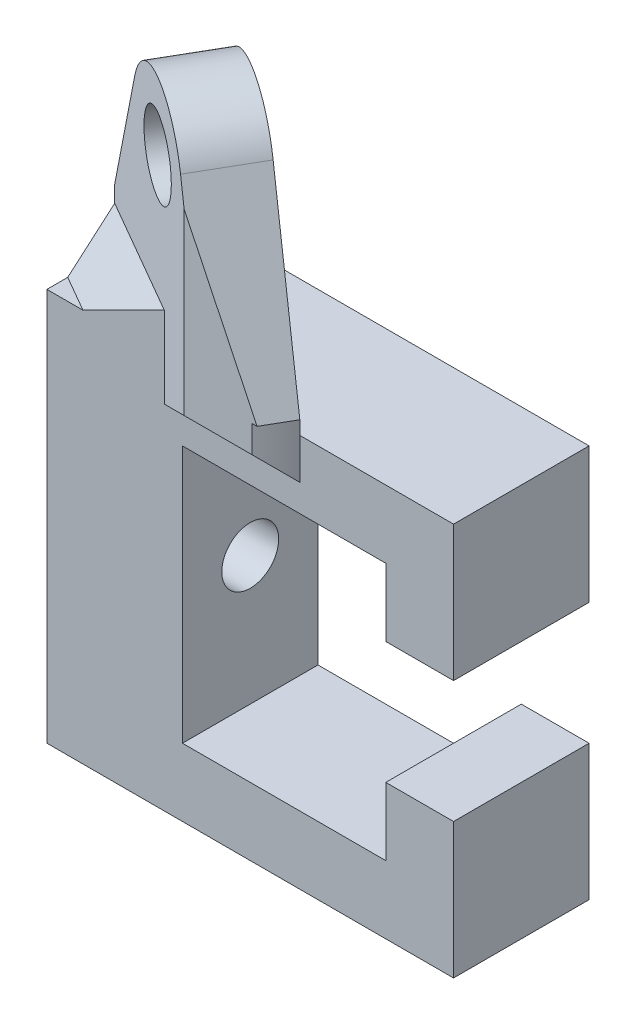
SolidWorks part; units mm, degrees
note: '?' marks a value the reader was unsure of.
ref_plane "Front Plane" through (0, 0, 0) normal (0, 0, 1) x (1, 0, 0)
ref_plane "Top Plane" through (0, 0, 0) normal (0, 1, 0) x (1, 0, 0)
ref_plane "Right Plane" through (0, 0, 0) normal (1, 0, 0) x (0, 0, -1)
sketch "Sketch1" plane through (0, 0, 0) normal (0, 0, 1) x (1, 0, 0)
  line L0 (0, 0) -> (0, -23031.2068) construction
  line L1 (0, 0) -> (23031.2068, 0) construction
  line L2 (15, 5) -> (15, 0)
  line L3 (15, 0) -> (0, 0)
  line L4 (0, 0) -> (0, 19)
  line L5 (0, 19) -> (15, 19)
  line L6 (15, 19) -> (15, 14)
  line L7 (15, 14) -> (20, 14)
  line L8 (20, 14) -> (20, 24)
  line L9 (20, 24) -> (-10, 24)
  line L10 (-10, 24) -> (-10, -5)
  line L11 (-10, -5) -> (20, -5)
  line L12 (20, -5) -> (20, 5)
  line L13 (20, 5) -> (15, 5)
  dimension "D1" = 19
  dimension "D2" = 15
  dimension "D3" = 15
  dimension "D4" = 5
  dimension "D5" = 5
  dimension "D6" = 5
  dimension "D7" = 5
  dimension "D8" = 5
  dimension "D9" = 10
extrude "Boss-Extrude1" add sketch "Sketch1" along normal mid plane 10
sketch "Sketch2" plane through (-10, 0, 0) normal (-1, 0, 0) x (0, 0, 1)
  line L0 (0, 24) -> (0, -49976) construction
  line L1 (5, 24) -> (-5, 24) construction
  line L2 (-5, 9.5) -> (49995, 9.5) construction
  line L3 (-5, 24) -> (-5, -5) construction
  circle A0 centre (0, 9.5) radius 2.1
  point P4 (0, 24)
  point P9 (-5, 9.5)
  dimension "D1" = 4.2
extrude "Cut-Extrude1" cut sketch "Sketch2" against normal blind 10
sketch "Sketch3" plane through (0, 24, 0) normal (0, 1, 0) x (1, 0, 0)
  line L0 (0, -5) -> (0, 5) construction
  line L1 (0, -5) -> (0, 5) construction
  circle A0 centre (0, 0) radius 10
  dimension "D1" = 20
extrude "Boss-Extrude2" add sketch "Sketch3" along normal blind 1
ref_axis "Axis1" through (0, 30.7, 0) along (0, -1, 0)?
ref_plane "Plane1" through (0, 0, 0) normal (-0.5, 0, 0.866) x (0, -1, 0)
sketch "Sketch4" plane through (0, 0, 0) normal (-0.5, 0, 0.866) x (0.866, 0, 0.5)
  line L0 (10, 25) -> (-10, 25) construction
  line L1 (10, 25) -> (-10, 25)
  line L2 (0, 29) -> (0, 50029) construction
  line L3 (-10, 25) -> (-4.6154, 37.9231)
  line L4 (10, 25) -> (4.6154, 37.9231)
  circle A0 centre (0, 36) radius 2.75
  circle A1 centre (0, 36) radius 10 construction
  arc A3 (4.6154, 37.9231) -> (-4.6154, 37.9231) centre (0, 36) ccw
  point P4 (0, 25)
  dimension "D1" = 5.5
  dimension "D2" = 20
  dimension "D3" = 11
  dimension "D4" = 10
extrude "Boss-Extrude3" add sketch "Sketch4" along normal blind 5
sketch "Sketch5" plane through (0, -5, 0) normal (0, -1, 0) x (1, 0, 0)
  line L0 (-20, -15) -> (30, -15)
  line L1 (30, -15) -> (30, 15)
  line L2 (30, 15) -> (-20, 15)
  line L3 (-20, 15) -> (-20, -15)
  line L4 (-10, -5) -> (20, -5)
  line L5 (20, -5) -> (20, 5)
  line L6 (20, 5) -> (-10, 5)
  line L7 (-10, 5) -> (-10, -5)
  line L8 (-10, -5) -> (20, -5)
  line L9 (20, -5) -> (20, 5)
  line L10 (20, 5) -> (-10, 5)
  line L11 (-10, 5) -> (-10, -5)
  line L12 (-12, -7) -> (22, -7)
  line L13 (22, -7) -> (22, 7)
  line L14 (22, 7) -> (-12, 7)
  line L15 (-12, 7) -> (-12, -7)
  dimension "D1" = 0
  dimension "D2" = 10
  dimension "D3" = 2
extrude "Cut-Extrude2" cut sketch "Sketch5" against normal through all contours L2 L3 L0 L1 L15 L14 L13 L12
sketch "Sketch6" plane through (0, 25, 0) normal (0, 1, 0) x (1, 0, 0)
  line L3 (7.1414, 7) -> (-7.1414, 7)
  line L4 (-8.6603, 5) -> (8.6603, -5)
  line L6 (7.1414, 7) -> (-7.1414, 7)
  line L7 (-8.6603, 5) -> (8.6603, -5)
  arc A1 (8.6603, -5) -> (7.1414, 7) centre (0, 0) ccw
  arc A2 (8.6603, -5) -> (7.1414, 7) centre (0, 0) ccw
  arc A4 (-7.1414, 7) -> (-8.6603, 5) centre (0, 0) ccw
  arc A5 (-7.1414, 7) -> (-8.6603, 5) centre (0, 0) ccw
  dimension "D1" = 0
extrude "Cut-Extrude3" cut sketch "Sketch6" against normal blind 1
sketch "Sketch7" plane through (0, 25, 0) normal (0, 1, 0) x (1, 0, 0)
  line L2 (-7.1414, -7) -> (2.1244, -7)
  line L3 (2.1244, -7) -> (-10, 0)
  line L4 (-7.1414, -7) -> (2.1244, -7)
  line L5 (2.1244, -7) -> (-10, 0)
  arc A1 (-10, 0) -> (-7.1414, -7) centre (0, 0) ccw
  arc A2 (-10, 0) -> (-7.1414, -7) centre (0, 0) ccw
  dimension "D1" = 0
extrude "Cut-Extrude4" cut sketch "Sketch7" against normal blind 1
chamfer "Chamfer1" distance 3 angle 45 1 edges at (-5.6699, 24, 2.5)
chamfer "Chamfer2" distance 3 angle 45 1 edges at (3.6603, 24, 5)
sketch "Sketch8" plane through (0, -5, 0) normal (0, -1, 0) x (1, 0, 0)
  line L0 (-10, 5) -> (-10, -5) construction
  line L1 (-10, -13.16) -> (-20.9807, -13.16)
  line L2 (-10, -13.16) -> (-10, 5.7861)
  line L3 (-10, 5.7861) -> (-20.9807, 5.7861)
  line L4 (-20.9807, -13.16) -> (-20.9807, 5.7861)
  point P5 (-11.2232, -13.16)
extrude "Cut-Extrude5" cut sketch "Sketch8" against normal through all
sketch "Sketch9" plane through (0, 24, 0) normal (0, 1, 0) x (1, 0, 0)
  line L2 (-8.6603, 5) -> (-10, 5)
  line L3 (-10, 5) -> (-10, 0)
  line L4 (-8.6603, 5) -> (-10, 5)
  line L5 (-10, 5) -> (-10, 0)
  arc A1 (-8.6603, 5) -> (-10, 0) centre (0, 0) ccw
  arc A2 (-8.6603, 5) -> (-10, 0) centre (0, 0) ccw
  dimension "D1" = 0
extrude "Boss-Extrude4" add sketch "Sketch9" along normal blind 1
